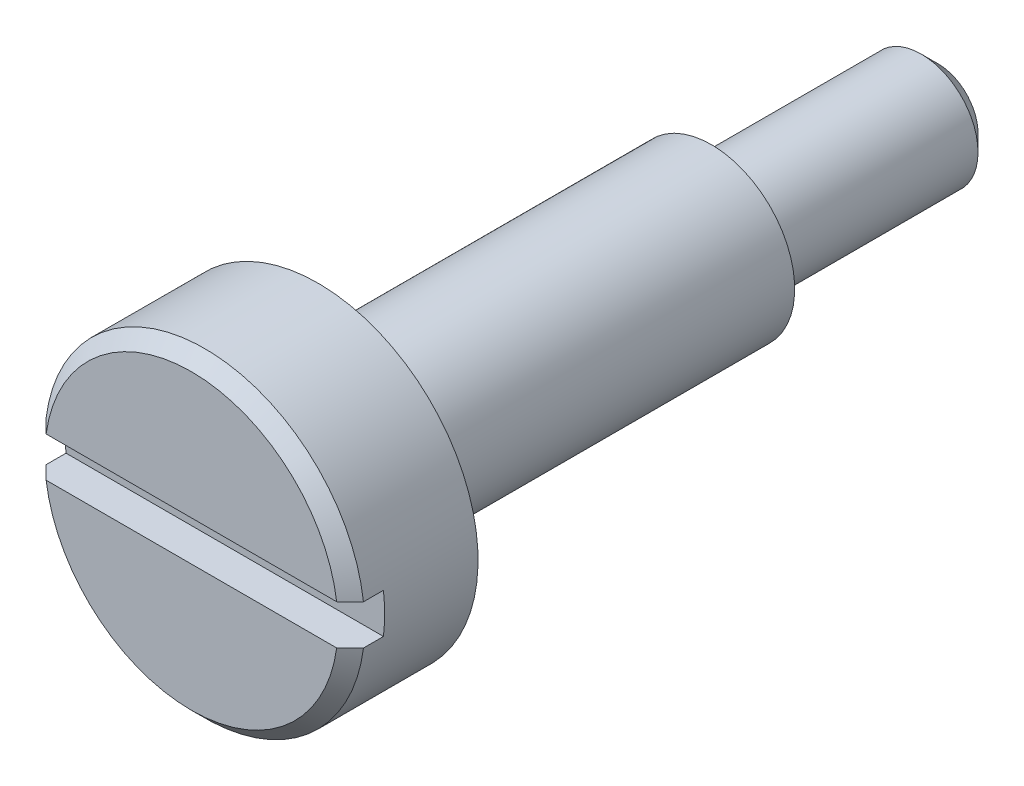
SolidWorks part; units mm, degrees
ref_plane "Front Plane" through (0, 0, 0) normal (0, 0, 1) x (1, 0, 0)
ref_plane "Top Plane" through (0, 0, 0) normal (0, 1, 0) x (1, 0, 0)
ref_plane "Right Plane" through (0, 0, 0) normal (1, 0, 0) x (0, 0, -1)
sketch "Sketch2" plane through (0, 0, 0) normal (0, 0, 1) x (1, 0, 0)
  circle A0 centre (0, 0) radius 2.4
  dimension "D1" = 4.8
extrude "Boss-Extrude1" add sketch "Sketch2" against normal blind 11.2 contours A0
sketch "Sketch4" plane through (0, 0, -11.2) normal (0, 0, -1) x (-1, 0, 0)
  circle A0 centre (0, 0) radius 1.25
  dimension "D1" = 2.5
extrude "Cut-Extrude1" cut sketch "Sketch4" against normal blind 9.3 flip side to cut
sketch "Sketch5" plane through (0, 0, -11.2) normal (0, 0, -1) x (-1, 0, 0)
  circle A0 centre (0, 0) radius 0.85
  dimension "D1" = 1.7
extrude "Cut-Extrude2" cut sketch "Sketch5" against normal blind 3.4 flip side to cut
sketch "Sketch6" plane through (0, 0, 0) normal (0, 0, 1) x (1, 0, 0)
  line L1 (-2.5, -0.3) -> (2.5, -0.3)
  line L2 (-2.5, -0.3) -> (-2.5, 0.3)
  line L3 (-2.5, 0.3) -> (2.5, 0.3)
  line L4 (2.5, -0.3) -> (2.5, 0.3)
  line L5 (-2.5, -0.3) -> (2.5, 0.3) construction
  line L6 (-2.5, 0.3) -> (2.5, -0.3) construction
  circle A3 centre (0, 0) radius 2.4 construction
  point P0 (0, 0)
  dimension "D1" = 0.6
  dimension "D2" = 0.1
extrude "Cut-Extrude3" cut sketch "Sketch6" against normal blind 0.5 contours L3 L4 L1 L2
chamfer "Chamfer1" distance 0.25 angle 45 1 edges at (-0.85, 0, -11.2)
fillet "Fillet1" radius 0.1 2 edges at (-1.25, 0, -1.9) (-0.85, 0, -7.8)
chamfer "Chamfer2" distance 0.2 angle 45 2 edges at (0, -2.4, 0) (0, 2.4, 0)
